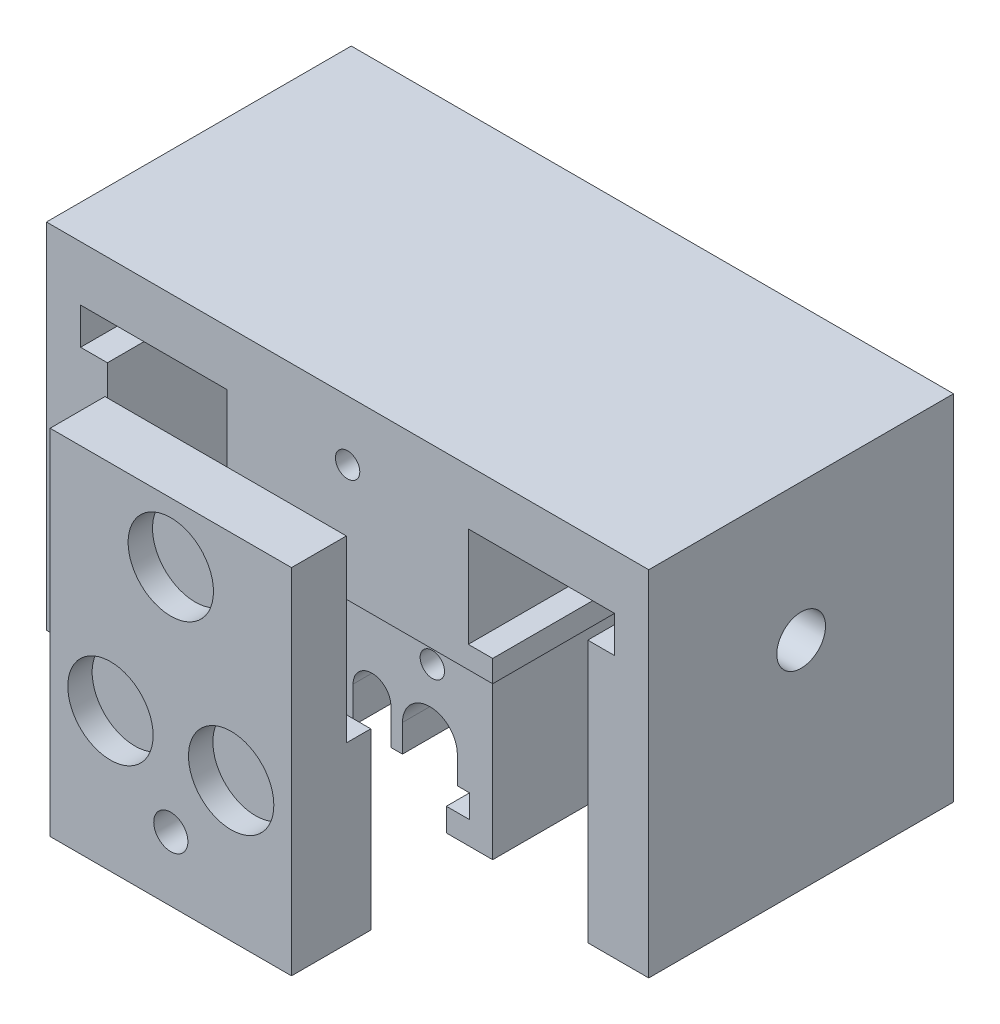
SolidWorks part; units mm, degrees
ref_plane "Front Plane" through (0, 0, 0) normal (0, 0, 1) x (1, 0, 0)
ref_plane "Top Plane" through (0, 0, 0) normal (0, 1, 0) x (1, 0, 0)
ref_plane "Right Plane" through (0, 0, 0) normal (1, 0, 0) x (0, 0, -1)
sketch "Sketch1" plane through (0, 0, 0) normal (0, 0, 1) x (1, 0, 0)
  line L0 (-21.9, 7) -> (-21.9, 10)
  line L1 (-21.9, 10) -> (-9.9, 10)
  line L2 (-9.9, 10) -> (-9.9, 1.8)
  line L3 (-9.9, -14.5) -> (9.9, -14.5)
  line L4 (9.9, -14.5) -> (9.9, 0)
  line L5 (9.9, 10) -> (21.9, 10)
  line L6 (21.9, 10) -> (21.9, 7)
  line L7 (19.7, -14.5) -> (24.7, -14.5)
  line L8 (24.7, -14.5) -> (24.7, 14.5)
  line L9 (24.7, 14.5) -> (-24.7, 14.5)
  line L14 (-24.7, 14.5) -> (-24.7, -14.5)
  line L16 (-21.9, 7) -> (-19.7, 7)
  line L17 (-19.7, 7) -> (-19.7, -14.5)
  line L18 (-19.7, -14.5) -> (-24.7, -14.5)
  line L19 (21.9, 7) -> (19.7, 7)
  line L20 (19.7, 7) -> (19.7, -14.5)
  line L22 (-9.9, 1.8) -> (-11.9, 1.8)
  line L23 (-11.9, 1.8) -> (-11.9, 0)
  line L24 (-11.9, 0) -> (-9.9, 0)
  line L25 (9.9, 1.8) -> (11.9, 1.8)
  line L26 (11.9, 1.8) -> (11.9, 0)
  line L27 (11.9, 0) -> (9.9, 0)
  line L28 (-9.9, 0) -> (-9.9, -14.5)
  line L29 (9.9, 1.8) -> (9.9, 10)
  point P9 (-24.7, 0)
  point P29 (0, -14.5)
  dimension "D1" = 19.8
  dimension "D2" = 12
  dimension "D3" = 4.5
  dimension "D4" = 4.5
  dimension "D5" = 24.5
  dimension "D6" = 5
  dimension "D7" = 2.2
  dimension "D8" = 1.8
  dimension "D9" = 14.5
  dimension "D10" = 3
  dimension "D11" = 2
extrude "Boss-Extrude1" add sketch "Sketch1" along normal blind 25
sketch "Sketch2" plane through (-24.7, 0, 0) normal (-1, 0, 0) x (0, 0, 1)
  line L0 (25, 1.8) -> (0, 1.8) construction
  line L2 (25, 1.8) -> (0, 1.8) construction
  line L3 (9.1108, 1.25) -> (17.7065, 1.25) construction
  circle A0 centre (12.5, 3.25) radius 2
  point P3 (12.5, 1.8)
  dimension "D1" = 4
  dimension "D2" = 0.55
extrude "Cut-Extrude1" cut sketch "Sketch2" against normal through all
sketch "Sketch5" plane through (0, 0, 0) normal (1, 0, 0) x (0, 0, -1)
  line L1 (-8.4008, 3.25) -> (-10.4504, 6.8)
  line L2 (-10.4504, 6.8) -> (-14.5496, 6.8)
  line L3 (-14.5496, 6.8) -> (-16.5992, 3.25)
  line L4 (-16.5992, 3.25) -> (-14.5496, -0.3)
  line L5 (-14.5496, -0.3) -> (-10.4504, -0.3)
  line L6 (-10.4504, -0.3) -> (-8.4008, 3.25)
  circle A2 centre (-12.5, 3.25) radius 3.55 construction
  dimension "D1" = 7.1
extrude "Cut-Extrude2" cut sketch "Sketch5" against normal blind 6 and the other way blind 6
sketch "Sketch6" plane through (0, 0, 0) normal (0, 0, 1) x (1, 0, 0)
  line L0 (6, 6.8) -> (-6, 6.8) construction
  line L1 (3, 6.8) -> (-3, 6.8)
  line L2 (3, 6.8) -> (3, -0.3)
  line L3 (3, -0.3) -> (-3, -0.3)
  line L4 (-3, 6.8) -> (-3, -0.3)
  line L5 (6, -0.3) -> (-6, -0.3) construction
  point P9 (0, -0.3)
  dimension "D1" = 6
extrude "Cut-Extrude3" cut sketch "Sketch6" along normal up to vertex (10.4504 mm away) up to point (-6, -0.3, 10.4504)
sketch "Sketch9" plane through (0, 0, 25) normal (0, 0, 1) x (1, 0, 0)
  line L2 (-6.1, -14.5) -> (6.1, -14.5)
  line L4 (-9.9, -14.5) -> (9.9, -14.5) construction
  line L5 (6.1, -14.5) -> (6.1, -12.6)
  line L6 (6.1, -12.6) -> (8, -12.6)
  line L7 (8, -12.6) -> (8, -10.7)
  line L8 (8, -10.7) -> (-8, -10.7)
  line L9 (-8, -10.7) -> (-8, -12.6)
  line L10 (-8, -12.6) -> (-6.1, -12.6)
  line L11 (-6.1, -12.6) -> (-6.1, -14.5)
  line L12 (-9.9, 0) -> (-9.9, -14.5) construction
  line L14 (-9.9, -12.6) -> (-8, -12.6) construction
  point P12 (0, -10.7)
  dimension "D1" = 1.9
extrude "Cut-Extrude4" cut sketch "Sketch9" against normal up to next
sketch "Sketch11" plane through (0, 0, 25) normal (0, 0, 1) x (1, 0, 0)
  line L0 (-8, -10.7) -> (-8, -12.6) construction
  line L2 (8, -12.6) -> (8, -10.7) construction
  line L3 (-7, -8.45) -> (-7, -10.7)
  line L4 (-2.5, -8.45) -> (-2.5, -10.7)
  line L5 (2.5, -8.45) -> (2.5, -10.7)
  line L6 (7, -8.45) -> (7, -10.7)
  line L7 (-7, -10.7) -> (-2.5, -10.7)
  line L8 (2.5, -10.7) -> (7, -10.7)
  line L9 (-4.75, -8.45) -> (-4.75, -6.2) construction
  line L10 (8, -10.7) -> (-8, -10.7) construction
  line L12 (-1.55, -7.75) -> (-1.55, -10.7)
  line L13 (-1.55, -10.7) -> (1.55, -10.7)
  line L14 (1.55, -7.75) -> (1.55, -10.7)
  arc A0 (-2.5, -8.45) -> (-7, -8.45) centre (-4.75, -8.45) ccw
  arc A1 (7, -8.45) -> (2.5, -8.45) centre (4.75, -8.45) ccw
  arc A2 (-1.55, -7.75) -> (1.55, -7.75) centre (0, -7.75) cw
  point P22 (0, -6.2)
  point P23 (4.75, -6.2)
  dimension "D1" = 4.5
  dimension "D2" = 1
  dimension "D3" = 1
  dimension "D4" = 3.1
extrude "Cut-Extrude5" cut sketch "Sketch11" against normal blind 23
sketch "Sketch12" plane through (0, 0, 25) normal (0, 0, 1) x (1, 0, 0)
  line L0 (6.1, -14.5) -> (9.9, -14.5) construction
  line L1 (-9.9, 0) -> (9.9, 0)
  line L2 (-9.9, 0) -> (-9.9, -14.5)
  line L3 (-9.9, -14.5) -> (9.9, -14.5)
  line L4 (9.9, 0) -> (9.9, -14.5)
  line L5 (-9.9, 0) -> (9.9, -14.5) construction
  line L6 (-9.9, -14.5) -> (9.9, 0) construction
  line L7 (-9.9, 0) -> (-9.9, -14.5) construction
  line L8 (9.9, -14.5) -> (9.9, 0) construction
  line L9 (9.9, 0) -> (11.9, 0) construction
  point P0 (0, -7.25)
extrude "Cut-Extrude6" cut sketch "Sketch12" against normal blind 2
sketch "Sketch13" plane through (0, 0, 23) normal (0, 0, 1) x (1, 0, 0)
  line L0 (0, 0) -> (0, -6.2) construction
  line L1 (9.9, 0) -> (-9.9, 0) construction
  line L2 (-9.9, -3.1) -> (0, -3.1) construction
  line L5 (-9.9, 0) -> (-9.9, -14.5) construction
  line L6 (0, -3.1) -> (9.9, -3.1) construction
  line L7 (9.9, -14.5) -> (9.9, 0) construction
  line L9 (6, 6.8) -> (-6, 6.8) construction
  line L10 (6, 6.8) -> (-6, 6.8) construction
  line L11 (6, -0.3) -> (-6, -0.3) construction
  line L12 (6, -0.3) -> (-6, -0.3) construction
  line L13 (-4.95, -3.1) -> (-4.95, -0.3) construction
  line L14 (0, 9.6) -> (0, 6.8) construction
  circle A0 centre (-4.95, -3.1) radius 1
  circle A1 centre (4.95, -3.1) radius 1
  arc A2 (1.55, -7.75) -> (-1.55, -7.75) centre (0, -7.75) ccw construction
  circle A3 centre (0, 9.6) radius 1
  point P15 (0, -3.1)
  point P20 (-4.95, -3.1)
  point P21 (4.95, -3.1)
  dimension "D1" = 2
extrude "Cut-Extrude7" cut sketch "Sketch13" against normal blind 12 and the other way blind 2
ref_plane "Plane1" through (0, 0, 35) normal (0, 0, 1) x (1, 0, 0)
sketch "Sketch14" plane through (0, 0, 35) normal (0, 0, 1) x (1, 0, 0)
  line L8 (-9.9, 14.5) -> (-9.9, -14.5)
  line L9 (-9.9, -14.5) -> (9.9, -14.5)
  line L10 (9.9, -14.5) -> (9.9, 14.5)
  line L11 (24.7, 14.5) -> (-24.7, 14.5) construction
  line L12 (9.9, 14.5) -> (-9.9, 14.5)
  circle A6 centre (0, 9.6) radius 1.25
  circle A7 centre (-4.95, -3.1) radius 1.25
  circle A8 centre (4.95, -3.1) radius 1.25
  dimension "D1" = 2.5
extrude "Boss-Extrude2" add sketch "Sketch14" along normal blind 4.5 separate body
sketch "Sketch15" plane through (0, 0, 35) normal (0, 0, -1) x (-1, 0, 0)
  line L0 (9.9, -0.2) -> (-9.9, -0.2)
  line L1 (9.9, 14.5) -> (9.9, -14.5) construction
  line L2 (11.9, 0) -> (-11.9, 0) construction
  line L4 (-9.9, -14.5) -> (-9.9, 14.5) construction
  line L5 (-9.9, -0.2) -> (-9.9, -14.5)
  line L6 (-9.9, -14.5) -> (9.9, -14.5)
  line L7 (9.9, -14.5) -> (9.9, -0.2)
  circle A0 centre (4.95, -3.1) radius 1.25 construction
  circle A1 centre (-4.95, -3.1) radius 1.25 construction
  circle A2 centre (4.95, -3.1) radius 1.25
  circle A3 centre (-4.95, -3.1) radius 1.25
  dimension "D1" = 0.2
extrude "Boss-Extrude3" add sketch "Sketch15" along normal blind 2
sketch "Sketch16" plane through (0, 0, 39.5) normal (0, 0, 1) x (1, 0, 0)
  circle A0 centre (4.95, -3.1) radius 3.5
  circle A1 centre (-4.95, -3.1) radius 3.5
  circle A2 centre (0, 9.6) radius 3.5
  dimension "D1" = 7
extrude "Cut-Extrude8" cut sketch "Sketch16" against normal blind 2
sketch "Sketch17" plane through (0, 0, 37.5) normal (0, 0, 1) x (1, 0, 0)
  circle A0 centre (0, 9.6) radius 1.25 construction
  circle A1 centre (-4.95, -3.1) radius 1.25 construction
  circle A2 centre (4.95, -3.1) radius 1.25 construction
  circle A3 centre (0, 9.6) radius 1.25
  circle A4 centre (-4.95, -3.1) radius 1.25
  circle A5 centre (4.95, -3.1) radius 1.25
extrude "Boss-Extrude4" add sketch "Sketch17" against normal blind 0.6
sketch "Sketch18" plane through (0, 0, 33) normal (0, 0, -1) x (-1, 0, 0)
  line L1 (-3.1754, -9.225) -> (-1.5877, -11.975)
  line L2 (-1.5877, -11.975) -> (1.5877, -11.975)
  line L3 (1.5877, -11.975) -> (3.1754, -9.225)
  line L4 (3.1754, -9.225) -> (1.5877, -6.475)
  line L5 (1.5877, -6.475) -> (-1.5877, -6.475)
  line L6 (-1.5877, -6.475) -> (-3.1754, -9.225)
  line L7 (1.55, -10.7) -> (1.55, -7.75) construction
  circle A1 centre (0, -9.225) radius 2.75 construction
  point P1 (0.0447, -9.0658)
  point P12 (0, 0)
  point P14 (1.55, -9.225)
  point P15 (3.1754, -9.225)
  dimension "D1" = 5.5
extrude "Cut-Extrude9" cut sketch "Sketch18" against normal blind 2.6
sketch "Sketch19" plane through (0, 0, 35.6) normal (0, 0, -1) x (-1, 0, 0)
  line L0 (1.5877, -6.475) -> (-1.5877, -6.475) construction
  circle A0 centre (0, -9.225) radius 1.4
  point P2 (0, 0)
  point P5 (0, -6.475)
  dimension "D1" = 2.8
extrude "Cut-Extrude10" cut sketch "Sketch19" against normal up to next (3.9 mm away)
